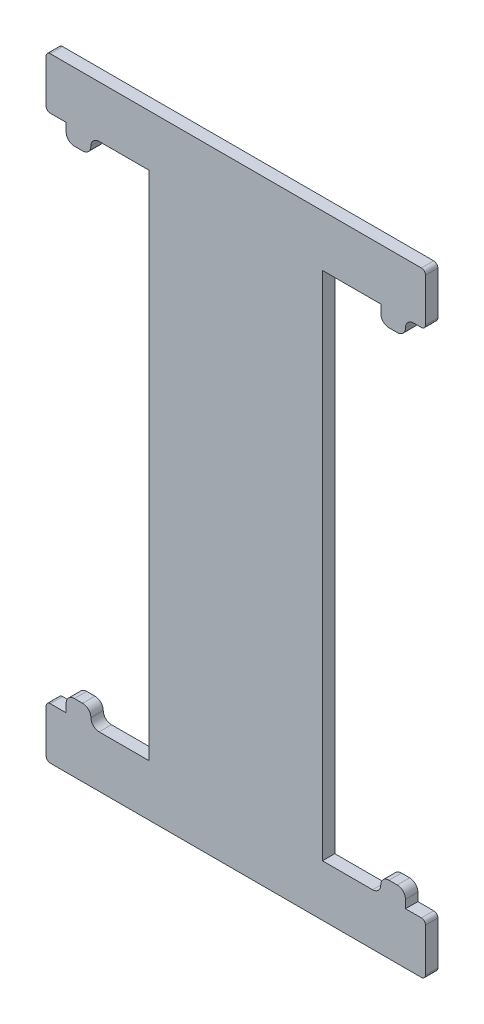
SolidWorks part; units mm, degrees
material "ABS"
ref_plane "前视基准面" through (0, 0, 0) normal (0, 0, 1) x (1, 0, 0)
ref_plane "上视基准面" through (0, 0, 0) normal (0, 1, 0) x (1, 0, 0)
ref_plane "右视基准面" through (0, 0, 0) normal (1, 0, 0) x (0, 0, -1)
other "Configuration Table"
sketch "草图1" plane through (0, 0, 0) normal (0, 0, 1) x (1, 0, 0)
  line L0 (-70.5706, 0) -> (16.54, 0) construction
  line L1 (0, 30.2544) -> (0, -24.4654) construction
  line L3 (-21, -74.5) -> (21, -74.5)
  line L4 (-21, -74.5) -> (-21, 74.5)
  line L5 (-21, 74.5) -> (21, 74.5)
  line L6 (21, -74.5) -> (21, 74.5)
  line L7 (-21, -74.5) -> (21, 74.5) construction
  line L8 (-21, 74.5) -> (21, -74.5) construction
  point P4 (0, 0)
  dimension "D1" = 149
  dimension "D2" = 42
extrude "凸台-拉伸1" add sketch "草图1" along normal blind 3
sketch "草图2" plane through (0, 0, 3) normal (0, 0, 1) x (1, 0, 0)
  line L0 (-50.6483, 0) -> (69.5569, 0) construction
  line L1 (21, -74.5) -> (46, -74.5)
  line L2 (21, -74.5) -> (21, -62)
  line L3 (21, -62) -> (46, -62)
  line L4 (46, -74.5) -> (46, -62)
  line L5 (0, 90.4915) -> (0, -100.3961) construction
  line L6 (-46, -74.5) -> (-46, -62)
  line L7 (-21, -62) -> (-46, -62)
  line L8 (-21, -74.5) -> (-21, -62)
  line L9 (-21, -74.5) -> (-46, -74.5)
  line L10 (-21, 74.5) -> (-46, 74.5)
  line L11 (-21, 74.5) -> (-21, 62)
  line L12 (-21, 62) -> (-46, 62)
  line L13 (-46, 74.5) -> (-46, 62)
  line L14 (46, 74.5) -> (46, 62)
  line L15 (21, 62) -> (46, 62)
  line L16 (21, 74.5) -> (21, 62)
  line L17 (21, 74.5) -> (46, 74.5)
  dimension "D1" = 12.5
  dimension "D2" = 25
extrude "凸台-拉伸2" add sketch "草图2" against normal up to surface (3 mm away) up to face at (0, 0, 0)
fillet "圆角1" radius 1 8 edges at (46, 74.5, 1.5) (46, 62, 1.5) (46, -62, 1.5) (46, -74.5, 1.5) (-46, -74.5, 1.5) (-46, -62, 1.5) (-46, 74.5, 1.5) (-46, 62, 1.5)
sketch "草图3" plane through (0, 0, 0) normal (0, 0, -1) x (-1, 0, 0)
  line L0 (0, 0) -> (50000, 0) construction
  line L1 (45, 62) -> (21, 62) construction
  line L2 (41.15, 62) -> (35.15, 62)
  line L3 (41.15, 62) -> (41.15, 58)
  line L4 (41.15, 58) -> (35.15, 58)
  line L5 (35.15, 62) -> (35.15, 58)
  line L6 (46, 73.5) -> (46, 63) construction
  line L7 (0, 0) -> (0, 50000) construction
  line L8 (-41.15, 58) -> (-35.15, 58)
  line L9 (-41.15, 62) -> (-41.15, 58)
  line L10 (-41.15, 62) -> (-35.15, 62)
  line L11 (-35.15, 62) -> (-35.15, 58)
  line L12 (-35.15, -62) -> (-35.15, -58)
  line L13 (-41.15, -62) -> (-35.15, -62)
  line L14 (-41.15, -62) -> (-41.15, -58)
  line L15 (-41.15, -58) -> (-35.15, -58)
  line L16 (35.15, -62) -> (35.15, -58)
  line L17 (41.15, -58) -> (35.15, -58)
  line L18 (41.15, -62) -> (41.15, -58)
  line L19 (41.15, -62) -> (35.15, -62)
  dimension "D1" = 4.85
  dimension "D2" = 4
  dimension "D3" = 6
extrude "凸台-拉伸3" add sketch "草图3" against normal up to surface (3 mm away) up to face at (0, 0, 3)
fillet "圆角2" radius 2 12 edges at (-41.15, -58, 1.5) (-35.15, -58, 1.5) (-35.15, -62, 1.5) (41.15, -58, 1.5) (35.15, -62, 1.5) (35.15, -58, 1.5) (35.15, 58, 1.5) (41.15, 58, 1.5) (-35.15, 58, 1.5) (-35.15, 62, 1.5) (-41.15, 58, 1.5) (41.15, 62, 1.5)
